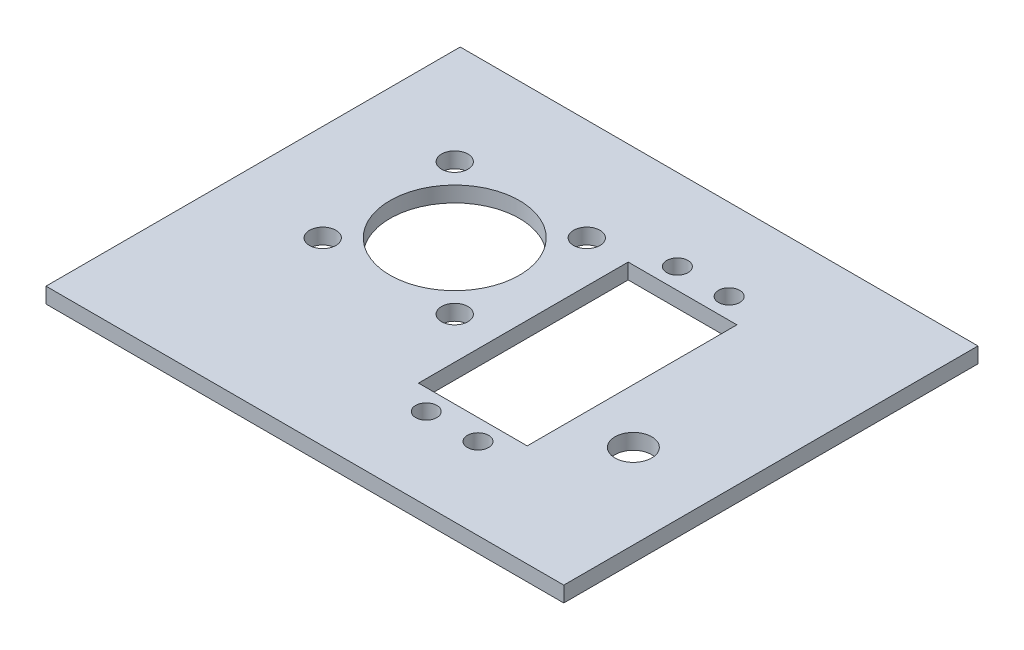
SolidWorks part; units mm, degrees
ref_plane "Płaszczyzna przednia" through (0, 0, 0) normal (0, 0, 1) x (1, 0, 0)
ref_plane "Płaszczyzna górna" through (0, 0, 0) normal (0, 1, 0) x (1, 0, 0)
ref_plane "Płaszczyzna prawa" through (0, 0, 0) normal (1, 0, 0) x (0, 0, -1)
sketch "Szkic1" plane through (0, 0, 0) normal (0, 1, 0) x (1, 0, 0)
  line L6 (-20.0188, 11.4569) -> (5.4812, -14.0431) construction
  line L11 (-38.6633, 31.161) -> (61.3367, 31.161)
  line L12 (-38.6633, 31.161) -> (-38.6633, -48.839)
  line L13 (-38.6633, -48.839) -> (61.3367, -48.839)
  line L14 (61.3367, 31.161) -> (61.3367, -48.839)
  line L15 (-20.0188, -14.0431) -> (5.4812, 11.4569) construction
  line L17 (13.5251, 11.411) -> (34.5251, 11.411)
  line L18 (13.5251, 11.411) -> (13.5251, -29.089)
  line L23 (13.5251, -29.089) -> (34.5251, -29.089)
  line L24 (34.5251, 11.411) -> (34.5251, -29.089)
  circle A0 centre (-7.2688, -1.2931) radius 12.5
  circle A2 centre (-20.0188, 11.4569) radius 2.55
  circle A3 centre (5.4812, 11.4569) radius 2.55
  circle A4 centre (5.4812, -14.0431) radius 2.55
  circle A5 centre (-20.0188, -14.0431) radius 2.55
  circle A6 centre (19.0251, 15.411) radius 2.05
  circle A7 centre (29.0251, 15.411) radius 2.05
  circle A8 centre (19.0251, -33.089) radius 2.05
  circle A9 centre (29.0251, -33.089) radius 2.05
  circle A10 centre (24.0251, -19.089) radius 0.5
  circle A11 centre (-7.2688, -1.2931) radius 0.5
  circle A12 centre (45.0251, -19.089) radius 3.55
  circle A13 centre (45.0251, -19.089) radius 0.5
  point P18 (24.0251, -29.089)
  point P22 (24.0251, 11.411)
  dimension "D3" = 10
  dimension "D5" = 4
  dimension "D13" = 36
  dimension "D18" = 19.75
  dimension "D20" = 5.1
  dimension "D22" = 25
  dimension "D23" = 7.1
  dimension "D24" = 4.1
  dimension "D1" = 100
  dimension "D2" = 80
  dimension "D4" = 10.5
  dimension "D6" = 4
  dimension "D7" = 5
  dimension "D8" = 5
  dimension "D9" = 4
  dimension "D10" = 4
  dimension "D11" = 5
  dimension "D12" = 5
  dimension "D14" = 21
  dimension "D15" = 40.5
  dimension "D16" = 21
  dimension "D17" = 10
  dimension "D19" = 19.75
  dimension "D21" = 25.5
extrude "Dodanie-wyciągnięcie1" add sketch "Szkic1" along normal blind 3 contours L14 L11 L12 L13 A12 A9 A8 A7 A6 A5 A4 A3 A2 A0 L17 L24 L23 L18 region at (11.0064, 0, 9.4427)
